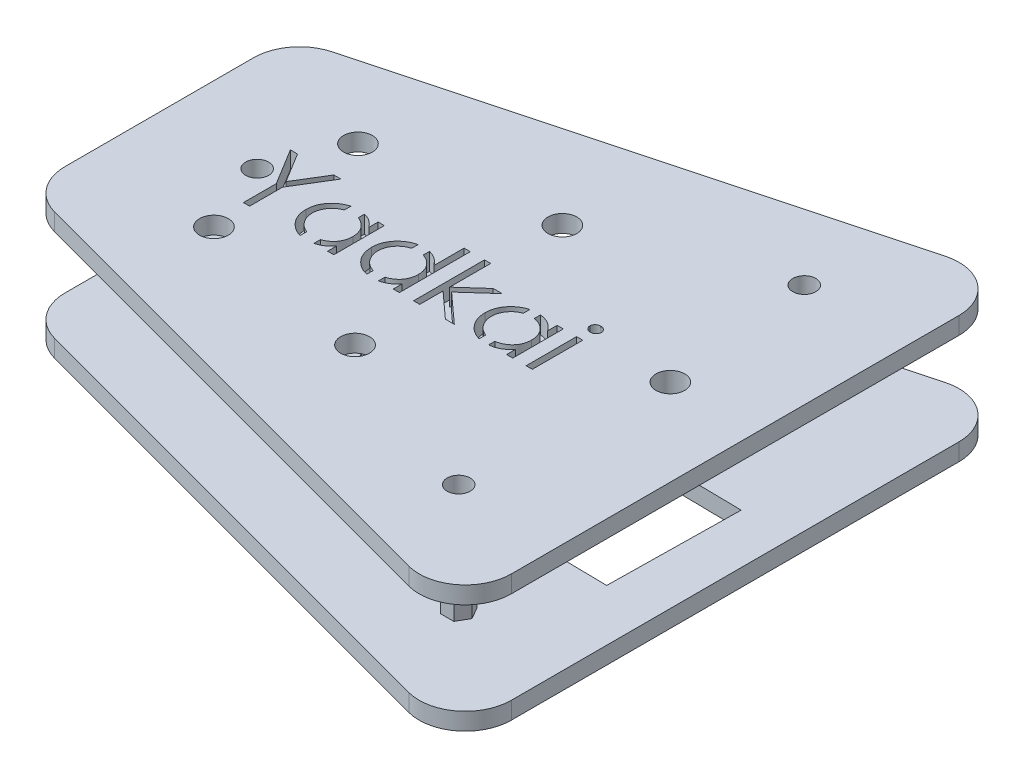
SolidWorks part; units mm, degrees
ref_plane "Alzado" through (0, 0, 0) normal (0, 0, 1) x (1, 0, 0)
ref_plane "Planta" through (0, 0, 0) normal (0, 1, 0) x (1, 0, 0)
ref_plane "Vista lateral" through (0, 0, 0) normal (1, 0, 0) x (0, 0, -1)
sketch "Croquis1" plane through (0, 0, 0) normal (0, 1, 0) x (1, 0, 0)
  line L0 (0, 16.3614) -> (0, -16.3614)
  line L1 (5.9294, -24.0888) -> (89.9294, -46.5965)
  line L2 (100, -38.8691) -> (100, 38.8691)
  line L3 (89.9294, 46.5965) -> (5.9294, 24.0888)
  line L4 (0, 0) -> (100, 0) construction
  line L5 (22, 12.5) -> (22, -12.5) construction
  line L6 (52, 18) -> (52, -18) construction
  line L7 (82, 30) -> (82, -30) construction
  circle A0 centre (22, 12.5) radius 2.5
  circle A1 centre (22, -12.5) radius 2.5
  circle A2 centre (52, 18) radius 2.5
  circle A3 centre (52, -18) radius 2.5
  arc A4 (100, 38.8691) -> (89.9294, 46.5965) centre (92, 38.8691) ccw
  arc A5 (89.9294, -46.5965) -> (100, -38.8691) centre (92, -38.8691) ccw
  arc A6 (0, -16.3614) -> (5.9294, -24.0888) centre (8, -16.3614) ccw
  arc A7 (0, 16.3614) -> (5.9294, 24.0888) centre (8, 16.3614) cw
  circle A8 centre (17, 0) radius 2
  circle A9 centre (82, -30) radius 2
  circle A10 centre (82, 30) radius 2
  point P3 (100, 0)
  point P10 (22, 0)
  point P15 (52, 0)
  point P18 (50, 0)
  point P25 (0, -22.5)
  point P28 (0, 22.5)
  point P35 (82, 0)
  dimension "D2" = 5
  dimension "D9" = 8
  dimension "D11" = 4
  dimension "D1" = 25
  dimension "D3" = 30
  dimension "D4" = 36
  dimension "D5" = 45
  dimension "D6" = 100
  dimension "D7" = 28
  dimension "D8" = 75
  dimension "D10" = 5
  dimension "D12" = 30
  dimension "D13" = 60
extrude "Saliente-Extruir1" add sketch "Croquis1" along normal blind 22
sketch "Croquis2" plane through (0, 0, 0) normal (0, 0, 1) x (1, 0, 0)
  line L0 (0, 22) -> (0, 0) construction
  line L1 (0, 19) -> (100, 19)
  line L2 (0, 19) -> (0, 3)
  line L3 (0, 3) -> (100, 3)
  line L4 (100, 19) -> (100, 3)
  line L5 (100, 22) -> (100, 0) construction
  point P8 (0, 11)
  dimension "D1" = 16
extrude "Cortar-Extruir1" cut sketch "Croquis2" against normal mid plane 100
sketch "Croquis3" plane through (0, 3, 0) normal (0, 1, 0) x (1, 0, 0)
  line L1 (17, -2.3094) -> (19, -1.1547)
  line L2 (19, -1.1547) -> (19, 1.1547)
  line L3 (19, 1.1547) -> (17, 2.3094)
  line L4 (17, 2.3094) -> (15, 1.1547)
  line L5 (15, 1.1547) -> (15, -1.1547)
  line L6 (15, -1.1547) -> (17, -2.3094)
  line L7 (80.8453, -32) -> (83.1547, -32)
  line L8 (83.1547, -32) -> (84.3094, -30)
  line L9 (84.3094, -30) -> (83.1547, -28)
  line L10 (83.1547, -28) -> (80.8453, -28)
  line L11 (80.8453, -28) -> (79.6906, -30)
  line L12 (79.6906, -30) -> (80.8453, -32)
  line L13 (84, 28.8453) -> (84, 31.1547)
  line L14 (84, 31.1547) -> (82, 32.3094)
  line L15 (82, 32.3094) -> (80, 31.1547)
  line L16 (80, 31.1547) -> (80, 28.8453)
  line L17 (80, 28.8453) -> (82, 27.6906)
  line L18 (82, 27.6906) -> (84, 28.8453)
  circle A0 centre (17, 0) radius 2 construction
  circle A1 centre (82, -30) radius 2 construction
  circle A2 centre (82, 30) radius 2 construction
  circle A3 centre (82, 30) radius 2 construction
  circle A4 centre (82, -30) radius 2 construction
  circle A5 centre (17, 0) radius 2 construction
extrude "Saliente-Extruir2" add sketch "Croquis3" along normal blind 16 separate body
sketch "Sketch1" plane through (0, 22, 0) normal (0, 1, 0) x (1, 0, 0)
  text T0 "Yadkai" font "Century Gothic" height 12
extrude "Cut-Extrude1" cut sketch "Sketch1" against normal blind 30
sketch "Sketch2" plane through (0, 22, 0) normal (0, 1, 0) x (1, 0, 0)
  line L1 (30.7767, 6.1651) -> (33.1549, 6.1651)
  line L2 (30.7767, 6.1651) -> (30.7767, -9.6611)
  line L3 (30.7767, -9.6611) -> (33.1549, -9.6611)
  line L4 (33.1549, 6.1651) -> (33.1549, -9.6611)
  line L5 (42.3834, 6.1651) -> (44.4013, 6.1651)
  line L6 (42.3834, 6.1651) -> (42.3834, -9.6611)
  line L7 (42.3834, -9.6611) -> (44.4013, -9.6611)
  line L8 (44.4013, 6.1651) -> (44.4013, -9.6611)
  line L9 (61.848, 6.1651) -> (63.5852, 6.1651)
  line L10 (61.848, 6.1651) -> (61.848, -9.6611)
  line L11 (61.848, -9.6611) -> (63.5852, -9.6611)
  line L12 (63.5852, 6.1651) -> (63.5852, -9.6611)
extrude "Boss-Extrude1" add sketch "Sketch2" against normal blind 3
sketch "Sketch3" plane through (0, 0, 0) normal (0, -1, 0) x (-1, 0, 0)
  line L1 (-32.5544, 5.7702) -> (-31.1627, 5.7702)
  line L2 (-32.5544, 5.7702) -> (-32.5544, -10.0666)
  line L3 (-32.5544, -10.0666) -> (-31.1627, -10.0666)
  line L4 (-31.1627, 5.7702) -> (-31.1627, -10.0666)
  line L5 (-44.4879, 7.9803) -> (-42.3516, 7.9803)
  line L6 (-44.4879, 7.9803) -> (-44.4879, -10.0666)
  line L7 (-44.4879, -10.0666) -> (-42.3516, -10.0666)
  line L8 (-42.3516, 7.9803) -> (-42.3516, -10.0666)
  line L9 (-64.1851, 7.9803) -> (-62.0427, 7.9803)
  line L10 (-64.1851, 7.9803) -> (-64.1851, -11.524)
  line L11 (-64.1851, -11.524) -> (-62.0427, -11.524)
  line L12 (-62.0427, 7.9803) -> (-62.0427, -11.524)
  point P12 (-64.1851, -1.7719)
extrude "Boss-Extrude2" add sketch "Sketch3" against normal blind 3
sketch "Sketch4" plane through (0, 22, 0) normal (0, 1, 0) x (1, 0, 0)
  circle A0 centre (84.9719, 3.7789) radius 2.5
sketch "Sketch6" plane through (0, 0, 0) normal (0, -1, 0) x (-1, 0, 0)
  line L8 (-91.0122, -13.315) -> (-78.4137, -13.1231)
  line L9 (-78.4137, -13.1231) -> (-78.764, 9.8742)
  line L10 (-78.764, 9.8742) -> (-91.3625, 9.6823)
  line L11 (-91.3625, 9.6823) -> (-91.0122, -13.315)
  line L12 (-91.0122, -13.315) -> (-78.4137, -13.1231)
  line L13 (-78.4137, -13.1231) -> (-78.764, 9.8742)
  line L14 (-78.764, 9.8742) -> (-91.3625, 9.6823)
  line L15 (-91.3625, 9.6823) -> (-91.0122, -13.315)
  dimension "D1" = 0.5
extrude "Cut-Extrude4" cut sketch "Sketch6" against normal blind 3
sketch "Sketch11" plane through (0, 22, 0) normal (0, 1, 0) x (1, 0, 0)
  circle A0 centre (84.9719, 3.7789) radius 9.6884
extrude "Boss-Extrude3" add sketch "Sketch11" against normal blind 7
sketch "Sketch5" plane through (0, 22, 0) normal (0, 1, 0) x (1, 0, 0)
  circle A0 centre (84.9719, 3.7789) radius 2.4945
  dimension "D1" = 4.9891
extrude "Cut-Extrude3" cut sketch "Sketch5" against normal blind 23
fillet "Fillet2" radius 0.7 1 edges at (84.9719, 15, 5.9094)
